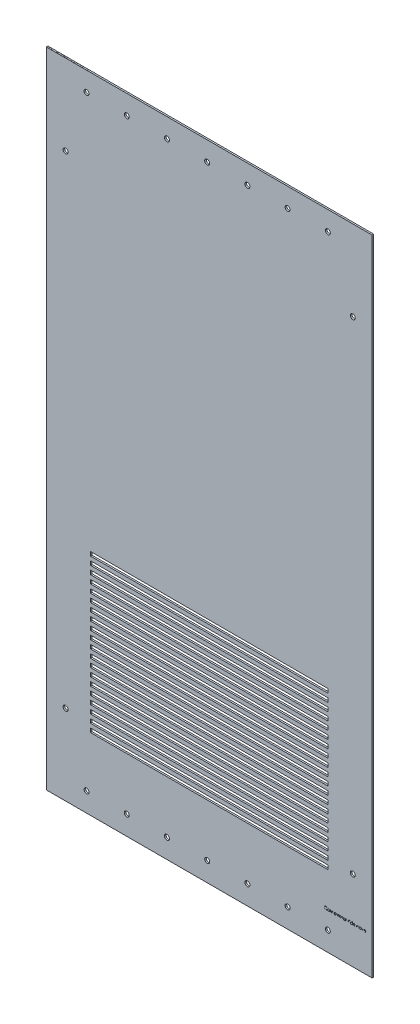
SolidWorks part; units mm, degrees
ref_plane "Front Plane" through (0, 0, 0) normal (0, 0, 1) x (1, 0, 0)
ref_plane "Top Plane" through (0, 0, 0) normal (0, 1, 0) x (1, 0, 0)
ref_plane "Right Plane" through (0, 0, 0) normal (1, 0, 0) x (0, 0, -1)
sketch "Sketch1" plane through (0, 0, 0) normal (0, 0, 1) x (1, 0, 0)
  line L0 (24, -100) -> (24, -571.3583) construction
  line L1 (0, 0) -> (405, 0)
  line L2 (0, 0) -> (0, -800)
  line L3 (0, -800) -> (405, -800)
  line L4 (405, 0) -> (405, -800)
  line L5 (24, -700) -> (381, -700) construction
  line L6 (381, -700) -> (381, -100) construction
  circle A0 centre (24, -100) radius 3.1
  circle A1 centre (381, -100) radius 3.1
  circle A2 centre (381, -700) radius 3.1
  circle A3 centre (24, -700) radius 3.1
  dimension "D8" = 6.2
  dimension "D1" = 405
  dimension "D2" = 800
  dimension "D3" = 24
  dimension "D4" = 100
  dimension "D5" = 24
  dimension "D6" = 100
  dimension "D7" = 100
extrude "Boss-Extrude1" add sketch "Sketch1" along normal blind 2
sketch "Sketch2" plane through (0, 0, 2) normal (0, 0, 1) x (1, 0, 0)
  line L0 (50, -24) -> (355, -24) construction
  line L1 (405, 0) -> (0, 0) construction
  line L2 (0, 0) -> (0, -800) construction
  line L3 (405, -800) -> (405, 0) construction
  line L4 (0, -400) -> (405, -400) construction
  line L5 (50, -776) -> (355, -776) construction
  circle A0 centre (50, -24) radius 3.1
  circle A1 centre (100, -24) radius 3.1
  circle A2 centre (150, -24) radius 3.1
  circle A3 centre (200, -24) radius 3.1
  circle A4 centre (250, -24) radius 3.1
  circle A5 centre (300, -24) radius 3.1
  circle A6 centre (350, -24) radius 3.1
  circle A7 centre (300, -776) radius 3.1
  circle A8 centre (250, -776) radius 3.1
  circle A9 centre (200, -776) radius 3.1
  circle A10 centre (150, -776) radius 3.1
  circle A11 centre (100, -776) radius 3.1
  circle A12 centre (50, -776) radius 3.1
  circle A13 centre (350, -776) radius 3.1
  dimension "D4" = 6.2
  dimension "D1" = 24
  dimension "D2" = 50
  dimension "D3" = 50
  dimension "D5" = 7
extrude "Cut-Extrude1" cut sketch "Sketch2" against normal through all
sketch "Sketch3" plane through (0, 0, 2) normal (0, 0, 1) x (1, 0, 0)
  line L0 (345.4109, -755.089) -> (399.6973, -755.089) construction
  line L1 (349.0904, -752.2312) -> (348.8156, -752.4415)
  line L2 (348.8156, -754.2364) -> (349.0904, -754.4446)
  line L3 (352.9045, -752.5313) -> (353.2186, -752.5313)
  line L4 (353.2186, -752.5313) -> (353.2186, -752.9758)
  line L5 (356.7186, -753.7035) -> (356.7186, -755.089)
  line L6 (356.7186, -755.089) -> (356.4045, -755.089)
  line L7 (356.4045, -755.089) -> (356.4045, -753.7021)
  line L8 (354.9686, -754.0941) -> (354.9686, -755.089)
  line L9 (354.9686, -755.089) -> (354.6545, -755.089)
  line L10 (354.6545, -755.089) -> (354.6545, -753.7884)
  line L11 (353.2186, -754.0127) -> (353.2186, -755.089)
  line L12 (353.2186, -755.089) -> (352.9045, -755.089)
  line L13 (352.9045, -755.089) -> (352.9045, -752.5313)
  line L14 (357.4366, -752.5313) -> (357.7507, -752.5313)
  line L15 (357.7507, -752.5313) -> (357.7507, -753.0045)
  line L16 (357.7507, -754.6255) -> (357.7507, -756.0313)
  line L17 (357.7507, -756.0313) -> (357.4366, -756.0313)
  line L18 (357.4366, -756.0313) -> (357.4366, -752.5313)
  line L19 (360.6673, -752.5313) -> (360.9814, -752.5313)
  line L20 (360.9814, -752.5313) -> (360.9814, -752.9078)
  line L21 (361.8789, -752.574) -> (361.7064, -752.8461)
  line L22 (360.9814, -754.2294) -> (360.9814, -755.089)
  line L23 (360.9814, -755.089) -> (360.6673, -755.089)
  line L24 (360.6673, -755.089) -> (360.6673, -752.5313)
  line L25 (364.2921, -754.2813) -> (364.5712, -754.4278)
  line L26 (364.7058, -753.8774) -> (362.4173, -753.8774)
  line L27 (362.4503, -753.5633) -> (364.3917, -753.5633)
  line L28 (366.5455, -752.8503) -> (366.3324, -753.0697)
  line L29 (365.1096, -754.7875) -> (365.3179, -754.5505)
  line L30 (368.4302, -752.8503) -> (368.217, -753.0697)
  line L31 (366.9943, -754.7875) -> (367.2025, -754.5505)
  line L32 (372.1994, -752.5313) -> (372.5135, -752.5313)
  line L33 (372.5135, -752.5313) -> (372.5135, -752.9078)
  line L34 (373.4109, -752.574) -> (373.2384, -752.8461)
  line L35 (372.5135, -754.2294) -> (372.5135, -755.089)
  line L36 (372.5135, -755.089) -> (372.1994, -755.089)
  line L37 (372.1994, -755.089) -> (372.1994, -752.5313)
  line L38 (376.2827, -752.8503) -> (376.0696, -753.0697)
  line L39 (374.8468, -754.7875) -> (375.0551, -754.5505)
  line L40 (376.9109, -752.5313) -> (377.225, -752.5313)
  line L41 (377.225, -752.5313) -> (377.225, -755.089)
  line L42 (377.225, -755.089) -> (376.9109, -755.089)
  line L43 (376.9109, -755.089) -> (376.9109, -752.5313)
  line L44 (380.5904, -751.4992) -> (380.5904, -755.089)
  line L45 (380.5904, -755.089) -> (380.2763, -755.089)
  line L46 (380.2763, -755.089) -> (380.2763, -754.6465)
  line L47 (380.2763, -753.0263) -> (380.2763, -751.4992)
  line L48 (380.2763, -751.4992) -> (380.5904, -751.4992)
  line L49 (383.4075, -754.2813) -> (383.6866, -754.4278)
  line L50 (383.8212, -753.8774) -> (381.5327, -753.8774)
  line L51 (381.5657, -753.5633) -> (383.5071, -753.5633)
  line L52 (388.3084, -753.0858) -> (388.0454, -753.2492)
  line L53 (388.0454, -754.371) -> (388.3084, -754.5435)
  line L54 (391.8532, -752.5313) -> (392.1933, -752.5313)
  line L55 (392.1933, -752.5313) -> (393.0423, -754.3934)
  line L56 (393.0423, -754.3934) -> (393.8914, -752.5313)
  line L57 (393.8914, -752.5313) -> (394.2314, -752.5313)
  line L58 (394.2314, -752.5313) -> (393.0648, -755.089)
  line L59 (393.0648, -755.089) -> (393.0199, -755.089)
  line L60 (393.0199, -755.089) -> (391.8532, -752.5313)
  line L61 (396.8691, -754.2813) -> (397.1481, -754.4278)
  line L62 (397.2827, -753.8774) -> (394.9943, -753.8774)
  line L63 (395.0272, -753.5633) -> (396.9686, -753.5633)
  line L64 (397.8212, -752.5313) -> (398.1353, -752.5313)
  line L65 (398.1353, -752.5313) -> (398.1353, -752.9078)
  line L66 (399.0327, -752.574) -> (398.8602, -752.8461)
  line L67 (398.1353, -754.2294) -> (398.1353, -755.089)
  line L68 (398.1353, -755.089) -> (397.8212, -755.089)
  line L69 (397.8212, -755.089) -> (397.8212, -752.5313)
  spline S0 degree 3 poles (348.8156, -752.4415) (348.7773, -752.3945) (348.7167, -752.3273) (348.629, -752.2455) (348.5611, -752.1882) (348.4894, -752.1368) (348.4155, -752.0886) (348.3383, -752.0453) (348.2316, -751.9928) (348.0919, -751.9381) (347.8544, -751.8758) (347.6689, -751.8576) (347.5437, -751.8582) knots 0 0 0 0 0.125475 0.187121 0.248294 0.309295 0.36985 0.430973 0.492456 0.616148 0.740844 1 1 1 1
  spline S1 degree 3 poles (347.5437, -751.8582) (347.4739, -751.8573) (347.3699, -751.8648) (347.2334, -751.8849) (347.1337, -751.907) (347.0362, -751.935) (346.9401, -751.9684) (346.8469, -752.0098) (346.7552, -752.0555) (346.6675, -752.1071) (346.5844, -752.1634) (346.5064, -752.2238) (346.4333, -752.2885) (346.3651, -752.3571) (346.3023, -752.4305) (346.2452, -752.5083) (346.1924, -752.5896) (346.1452, -752.6742) (346.1057, -752.7622) (346.0707, -752.8524) (346.043, -752.9455) (346.0211, -753.041) (346.0006, -753.1732) (345.9934, -753.2742) (345.9943, -753.3425) knots 0 0 0 0 0.087502 0.130463 0.172752 0.215403 0.25765 0.300153 0.343121 0.385925 0.427686 0.468818 0.509492 0.549883 0.58998 0.630405 0.670869 0.711384 0.751627 0.791776 0.832459 0.873319 0.914543 1 1 1 1
  spline S2 degree 3 poles (345.9943, -753.3425) (345.9938, -753.4441) (346.0079, -753.5941) (346.0536, -753.787) (346.1038, -753.9224) (346.1657, -754.0523) (346.2439, -754.1746) (346.3345, -754.291) (346.4388, -754.3988) (346.5532, -754.4974) (346.676, -754.5841) (346.8068, -754.6564) (346.9441, -754.7166) (347.0892, -754.7628) (347.2958, -754.8072) (347.4565, -754.8206) (347.5655, -754.8197) knots 0 0 0 0 0.12629 0.186726 0.246146 0.305576 0.365429 0.426326 0.48884 0.551725 0.613919 0.675484 0.737334 0.800229 0.864502 1 1 1 1
  spline S3 degree 3 poles (347.5655, -754.8197) (347.6856, -754.8198) (347.8641, -754.8028) (348.092, -754.7408) (348.2534, -754.677) (348.4067, -754.5939) (348.6042, -754.4576) (348.7349, -754.3292) (348.8156, -754.2364) knots 0 0 0 0 0.252949 0.374755 0.49594 0.617181 0.740909 1 1 1 1
  spline S4 degree 3 poles (349.0904, -754.4446) (349.0471, -754.5022) (348.9783, -754.5848) (348.8774, -754.6859) (348.7978, -754.756) (348.7147, -754.8222) (348.6266, -754.8825) (348.5347, -754.9378) (348.4394, -754.9884) (348.3406, -755.0333) (348.2386, -755.0718) (348.1338, -755.1049) (348.0261, -755.1321) (347.9154, -755.1534) (347.7626, -755.1727) (347.646, -755.1793) (347.5676, -755.1787) knots 0 0 0 0 0.123053 0.183475 0.243727 0.304279 0.364863 0.425946 0.487391 0.54922 0.611144 0.673529 0.736961 0.800785 0.866013 1 1 1 1
  spline S5 degree 3 poles (347.5676, -755.1787) (347.4931, -755.1796) (347.383, -755.1737) (347.2386, -755.1581) (347.1348, -755.1408) (347.0337, -755.1205) (346.9361, -755.0932) (346.8412, -755.0627) (346.7492, -755.0268) (346.6602, -754.9863) (346.5743, -754.9405) (346.4917, -754.8898) (346.4115, -754.8353) (346.3349, -754.7753) (346.236, -754.6887) (346.167, -754.6173) (346.124, -754.5666) knots 0 0 0 0 0.13775 0.203917 0.26878 0.332414 0.394754 0.45618 0.516996 0.577396 0.637198 0.696999 0.756756 0.816554 0.876948 1 1 1 1
  spline S6 degree 3 poles (346.124, -754.5666) (346.0514, -754.4819) (345.954, -754.3461) (345.8508, -754.1497) (345.7884, -753.9964) (345.7397, -753.8363) (345.6937, -753.6109) (345.6798, -753.4365) (345.6802, -753.3186) knots 0 0 0 0 0.247156 0.36878 0.490734 0.613614 0.738958 1 1 1 1
  spline S7 degree 3 poles (345.6802, -753.3186) (345.6801, -753.1948) (345.6958, -753.0113) (345.7526, -752.7759) (345.812, -752.6097) (345.8873, -752.4505) (345.9803, -752.2997) (346.09, -752.1562) (346.2154, -752.0222) (346.353, -751.8996) (346.5003, -751.7918) (346.6571, -751.7021) (346.8216, -751.6271) (346.9951, -751.5695) (347.2417, -751.5146) (347.4336, -751.4995) (347.5634, -751.4992) knots 0 0 0 0 0.127014 0.187955 0.248014 0.307748 0.368235 0.42947 0.492743 0.556258 0.618217 0.679655 0.741246 0.803415 0.866815 1 1 1 1
  spline S8 degree 3 poles (347.5634, -751.4992) (347.6429, -751.4991) (347.7611, -751.5045) (347.9156, -751.5255) (348.0272, -751.5466) (348.1363, -751.5728) (348.2421, -751.6069) (348.3452, -751.646) (348.445, -751.6909) (348.5409, -751.7414) (348.6329, -751.7968) (348.7204, -751.8571) (348.8039, -751.9218) (348.882, -751.9922) (348.9822, -752.0913) (349.0482, -752.1745) (349.0904, -752.2312) knots 0 0 0 0 0.135683 0.201215 0.265682 0.329267 0.392395 0.45507 0.517127 0.57879 0.63974 0.700192 0.759806 0.819628 0.879355 1 1 1 1
  spline S9 degree 3 poles (350.954, -752.4864) (351.0481, -752.4854) (351.1873, -752.499) (351.3654, -752.5436) (351.4912, -752.5888) (351.6096, -752.6496) (351.762, -752.7471) (351.8636, -752.8398) (351.9257, -752.9078) knots 0 0 0 0 0.258332 0.382134 0.503804 0.624693 0.746871 1 1 1 1
  spline S10 degree 3 poles (351.9257, -752.9078) (351.9828, -752.9701) (352.0592, -753.07) (352.1414, -753.2144) (352.1905, -753.3266) (352.2292, -753.443) (352.2663, -753.6059) (352.2758, -753.7322) (352.2763, -753.8171) knots 0 0 0 0 0.253834 0.376506 0.498534 0.621368 0.744565 1 1 1 1
  spline S11 degree 3 poles (352.2763, -753.8171) (352.2768, -753.9027) (352.2651, -754.0298) (352.2265, -754.1942) (352.1857, -754.3121) (352.1333, -754.4259) (352.0694, -754.5353) (351.9936, -754.6405) (351.9076, -754.7405) (351.8125, -754.8327) (351.7094, -754.913) (351.6002, -754.9818) (351.4836, -755.0373) (351.3605, -755.0809) (351.1845, -755.1228) (351.0469, -755.1335) (350.954, -755.1338) knots 0 0 0 0 0.123337 0.183265 0.243172 0.302898 0.363774 0.425605 0.489659 0.553785 0.616222 0.677854 0.739517 0.802097 0.865866 1 1 1 1
  spline S12 degree 3 poles (350.954, -755.1338) (350.8606, -755.1334) (350.7226, -755.1229) (350.546, -755.0809) (350.4228, -755.0371) (350.3057, -754.9818) (350.1959, -754.9132) (350.0927, -754.8326) (349.9976, -754.7405) (349.9116, -754.6405) (349.8357, -754.5353) (349.7719, -754.4259) (349.7195, -754.3121) (349.6787, -754.1942) (349.6401, -754.0298) (349.6284, -753.9027) (349.6289, -753.8171) knots 0 0 0 0 0.134635 0.198324 0.260825 0.322714 0.384555 0.446913 0.510958 0.574931 0.636685 0.697483 0.757134 0.816966 0.876818 1 1 1 1
  spline S13 degree 3 poles (349.6289, -753.8171) (349.6294, -753.7324) (349.6389, -753.6064) (349.6759, -753.4439) (349.7146, -753.328) (349.7642, -753.2162) (349.8453, -753.0715) (349.923, -752.9724) (349.9794, -752.9099) knots 0 0 0 0 0.255238 0.378679 0.501088 0.622714 0.746241 1 1 1 1
  spline S14 degree 3 poles (349.9794, -752.9099) (350.041, -752.841) (350.1436, -752.7492) (350.2956, -752.6497) (350.4153, -752.5901) (350.5409, -752.5434) (350.7198, -752.499) (350.8594, -752.4855) (350.954, -752.4864) knots 0 0 0 0 0.252713 0.374819 0.496436 0.617911 0.741288 1 1 1 1
  spline S15 degree 3 poles (350.9526, -752.8005) (350.8856, -752.8007) (350.7861, -752.8097) (350.6581, -752.8408) (350.5667, -752.8734) (350.479, -752.9155) (350.3951, -752.9672) (350.3147, -753.0278) (350.2393, -753.0973) (350.1701, -753.1732) (350.1096, -753.254) (350.0582, -753.3385) (350.0154, -753.4268) (349.9835, -753.5197) (349.952, -753.6499) (349.9432, -753.7511) (349.943, -753.8192) knots 0 0 0 0 0.126044 0.187165 0.247399 0.30838 0.36978 0.432584 0.497641 0.562401 0.625557 0.687332 0.748313 0.809791 0.871768 1 1 1 1
  spline S16 degree 3 poles (349.943, -753.8192) (349.9432, -753.9079) (349.9588, -754.0412) (350.0171, -754.2092) (350.0757, -754.3288) (350.1491, -754.4395) (350.2356, -754.5382) (350.3342, -754.6233) (350.4438, -754.694) (350.5622, -754.7501) (350.7306, -754.804) (350.8633, -754.8207) (350.9526, -754.8197) knots 0 0 0 0 0.168179 0.251488 0.335841 0.419834 0.502345 0.583649 0.665931 0.748717 0.831047 1 1 1 1
  spline S17 degree 3 poles (350.9526, -754.8197) (351.0419, -754.8206) (351.1744, -754.8042) (351.3425, -754.7499) (351.4607, -754.6941) (351.5703, -754.6231) (351.6696, -754.5386) (351.7554, -754.4392) (351.8287, -754.3287) (351.8882, -754.2094) (351.9462, -754.0412) (351.962, -753.9079) (351.9622, -753.8192) knots 0 0 0 0 0.168983 0.250908 0.333708 0.416005 0.49766 0.579893 0.663902 0.748466 0.831791 1 1 1 1
  spline S18 degree 3 poles (351.9622, -753.8192) (351.962, -753.7511) (351.9531, -753.6499) (351.9217, -753.5197) (351.8898, -753.4268) (351.8471, -753.3383) (351.7947, -753.2543) (351.7345, -753.1729) (351.6644, -753.0975) (351.5891, -753.0278) (351.5087, -752.9672) (351.4249, -752.9157) (351.3375, -752.873) (351.2461, -752.8411) (351.1185, -752.8095) (351.0193, -752.8008) (350.9526, -752.8005) knots 0 0 0 0 0.128274 0.19027 0.251768 0.312769 0.374793 0.43797 0.503047 0.568125 0.63095 0.692369 0.752973 0.813641 0.874355 1 1 1 1
  spline S19 degree 3 poles (353.2186, -752.9758) (353.2713, -752.9003) (353.3777, -752.7674) (353.5077, -752.6573) (353.5734, -752.6161) knots 0 0 0 0 0.543395 1 1 1 1
  spline S20 degree 3 poles (353.5734, -752.6161) (353.655, -752.574) (353.8268, -752.5073) (354.0099, -752.4871) (354.1006, -752.4864) knots 0 0 0 0 0.503035 1 1 1 1
  spline S21 degree 3 poles (354.1006, -752.4864) (354.1617, -752.4872) (354.2533, -752.4949) (354.3711, -752.5263) (354.4557, -752.5586) (354.5354, -752.5979) (354.6085, -752.6439) (354.6741, -752.6956) (354.7323, -752.7553) (354.7845, -752.8246) (354.8523, -752.9384) (354.8911, -753.0355) (354.9146, -753.1041) knots 0 0 0 0 0.166532 0.248836 0.331246 0.412957 0.490494 0.566156 0.639987 0.716765 0.802144 1 1 1 1
  spline S22 degree 3 poles (354.9146, -753.1041) (354.9407, -753.055) (354.9838, -752.9846) (355.0481, -752.8974) (355.0981, -752.8374) (355.1506, -752.7821) (355.2056, -752.7313) (355.263, -752.6848) (355.3428, -752.6305) (355.4466, -752.5729) (355.6212, -752.5057) (355.7604, -752.4862) (355.8527, -752.4864) knots 0 0 0 0 0.141226 0.209116 0.27484 0.339483 0.402476 0.464942 0.526833 0.647415 0.765562 1 1 1 1
  spline S23 degree 3 poles (355.8527, -752.4864) (355.9364, -752.487) (356.0614, -752.5007) (356.2157, -752.5587) (356.3211, -752.6169) (356.4163, -752.6901) (356.499, -752.7772) (356.5688, -752.8775) (356.6144, -752.9719) (356.6453, -753.0553) (356.6643, -753.1263) (356.6812, -753.2044) (356.6952, -753.2898) (356.7054, -753.3827) (356.7159, -753.5213) (356.719, -753.6292) (356.7186, -753.7035) knots 0 0 0 0 0.147965 0.218797 0.28947 0.359724 0.429708 0.500497 0.574429 0.613947 0.657155 0.703973 0.754939 0.809707 0.868833 1 1 1 1
  spline S24 degree 3 poles (356.4045, -753.7021) (356.4046, -753.6393) (356.4036, -753.5489) (356.3965, -753.434) (356.3906, -753.3598) (356.3823, -753.2936) (356.3717, -753.2354) (356.3604, -753.1848) (356.3417, -753.1287) (356.3117, -753.0668) (356.2661, -753.0001) (356.2086, -752.942) (356.1423, -752.8916) (356.0667, -752.8507) (355.9529, -752.8104) (355.8605, -752.8001) (355.798, -752.8005) knots 0 0 0 0 0.150563 0.216151 0.27568 0.328707 0.375904 0.417302 0.452693 0.517265 0.581217 0.645322 0.712024 0.78013 0.850218 1 1 1 1
  spline S25 degree 3 poles (355.798, -752.8005) (355.7195, -752.7991) (355.6025, -752.8184) (355.4556, -752.8764) (355.3533, -752.9388) (355.2593, -753.0136) (355.1784, -753.1026) (355.1116, -753.2032) (355.0663, -753.2963) (355.0377, -753.38) (355.0189, -753.4531) (355.0042, -753.5362) (354.9904, -753.6287) (354.9814, -753.7313) (354.9701, -753.8872) (354.9691, -754.0095) (354.9686, -754.0941) knots 0 0 0 0 0.134707 0.201865 0.270788 0.340024 0.408083 0.476813 0.547346 0.58564 0.628865 0.677153 0.730803 0.789807 0.854325 1 1 1 1
  spline S26 degree 3 poles (354.6545, -753.7884) (354.6546, -753.7178) (354.6536, -753.6165) (354.6465, -753.4878) (354.6406, -753.405) (354.6322, -753.3315) (354.6226, -753.2671) (354.6112, -753.2119) (354.5924, -753.1514) (354.5637, -753.0846) (354.5175, -753.0135) (354.4599, -752.9512) (354.3923, -752.8981) (354.3163, -752.8542) (354.202, -752.8109) (354.1086, -752.801) (354.0459, -752.8005) knots 0 0 0 0 0.158779 0.227738 0.289946 0.345499 0.393896 0.436374 0.472122 0.536384 0.599078 0.661948 0.726311 0.791771 0.858647 1 1 1 1
  spline S27 degree 3 poles (354.0459, -752.8005) (353.9701, -752.7999) (353.8562, -752.8181) (353.7134, -752.8756) (353.6114, -752.9352) (353.5177, -753.0091) (353.4357, -753.096) (353.3668, -753.1949) (353.3211, -753.287) (353.2916, -753.3686) (353.272, -753.4379) (353.2551, -753.5149) (353.2426, -753.5998) (353.2305, -753.6921) (353.2224, -753.8306) (353.2176, -753.9383) (353.2186, -754.0127) knots 0 0 0 0 0.136871 0.206114 0.277538 0.349772 0.421251 0.492911 0.567027 0.606614 0.649704 0.697303 0.749086 0.804881 0.865485 1 1 1 1
  spline S28 degree 3 poles (357.7507, -753.0045) (357.8128, -752.9192) (357.9173, -752.8033) (358.0785, -752.6791) (358.2057, -752.6077) (358.3401, -752.5539) (358.5313, -752.4998) (358.6824, -752.4867) (358.7841, -752.4864) knots 0 0 0 0 0.263045 0.386061 0.505771 0.625178 0.746148 1 1 1 1
  spline S29 degree 3 poles (358.7841, -752.4864) (358.8738, -752.4873) (359.007, -752.4972) (359.1785, -752.538) (359.3, -752.5814) (359.4173, -752.635) (359.5285, -752.7028) (359.6354, -752.7812) (359.7354, -752.8714) (359.8277, -752.969) (359.9075, -753.0741) (359.9764, -753.183) (360.0321, -753.2976) (360.0756, -753.4169) (360.1176, -753.5847) (360.1284, -753.7153) (360.1289, -753.8031) knots 0 0 0 0 0.128636 0.190653 0.252125 0.313446 0.375227 0.438498 0.503285 0.56801 0.630879 0.692154 0.752552 0.813191 0.873985 1 1 1 1
  spline S30 degree 3 poles (360.1289, -753.8031) (360.1287, -753.8926) (360.1171, -754.0253) (360.0765, -754.196) (360.0335, -754.3173) (359.9778, -754.4333) (359.9101, -754.5439) (359.8302, -754.6491) (359.7389, -754.7474) (359.6399, -754.838) (359.534, -754.9173) (359.4229, -754.9838) (359.3073, -755.0394) (359.186, -755.0812) (359.0157, -755.1222) (358.8832, -755.1335) (358.7939, -755.1338) knots 0 0 0 0 0.128034 0.189574 0.25058 0.311733 0.37325 0.435763 0.500346 0.564949 0.627528 0.689157 0.749865 0.81076 0.8723 1 1 1 1
  spline S31 degree 3 poles (358.7939, -755.1338) (358.6935, -755.135) (358.545, -755.1178) (358.3546, -755.0653) (358.2204, -755.0086) (358.0923, -754.9363) (357.9272, -754.8168) (357.8182, -754.7057) (357.7507, -754.6255) knots 0 0 0 0 0.250548 0.37123 0.492116 0.613401 0.737997 1 1 1 1
  spline S32 degree 3 poles (358.7813, -752.8005) (358.7112, -752.7995) (358.6078, -752.8095) (358.4741, -752.8391) (358.38, -752.872) (358.2897, -752.9124) (358.2041, -752.9629) (358.123, -753.0226) (358.0468, -753.0902) (357.9779, -753.1648) (357.917, -753.2444) (357.8657, -753.3289) (357.8232, -753.4175) (357.7909, -753.511) (357.7597, -753.6431) (357.7509, -753.7462) (357.7507, -753.8157) knots 0 0 0 0 0.130024 0.192374 0.253884 0.314896 0.375806 0.438242 0.501591 0.564881 0.626533 0.687516 0.748106 0.808796 0.870822 1 1 1 1
  spline S33 degree 3 poles (357.7507, -753.8157) (357.7508, -753.9065) (357.766, -754.0416) (357.822, -754.2114) (357.8805, -754.3289) (357.9544, -754.4369) (358.0435, -754.5336) (358.147, -754.6183) (358.263, -754.6898) (358.3875, -754.7477) (358.5606, -754.8034) (358.6961, -754.8196) (358.7862, -754.8197) knots 0 0 0 0 0.169344 0.251061 0.332326 0.413189 0.494299 0.576654 0.661785 0.747765 0.831967 1 1 1 1
  spline S34 degree 3 poles (358.7862, -754.8197) (358.8747, -754.8203) (359.0069, -754.8024) (359.1758, -754.7474) (359.296, -754.688) (359.4088, -754.6149) (359.5107, -754.5274) (359.5997, -754.4259) (359.6756, -754.3129) (359.7366, -754.1917) (359.7979, -754.0253) (359.8138, -753.8934) (359.8148, -753.8066) knots 0 0 0 0 0.165574 0.248159 0.332033 0.416257 0.499525 0.583039 0.668596 0.754035 0.83692 1 1 1 1
  spline S35 degree 3 poles (359.8148, -753.8066) (359.816, -753.7191) (359.7964, -753.5882) (359.7389, -753.4207) (359.6764, -753.3012) (359.6022, -753.1884) (359.5125, -753.0889) (359.4118, -753.0017) (359.2992, -752.9297) (359.1782, -752.8725) (359.0072, -752.8159) (358.8718, -752.8009) (358.7813, -752.8005) knots 0 0 0 0 0.163349 0.245826 0.330367 0.415198 0.497941 0.580476 0.66374 0.747513 0.830399 1 1 1 1
  spline S36 degree 3 poles (360.9814, -752.9078) (361.0245, -752.8401) (361.0924, -752.7463) (361.1982, -752.6436) (361.2758, -752.5851) (361.3562, -752.5413) (361.4638, -752.4986) (361.5494, -752.4868) (361.6054, -752.4864) knots 0 0 0 0 0.306112 0.438367 0.560541 0.675317 0.786114 1 1 1 1
  spline S37 degree 3 poles (361.6054, -752.4864) (361.6504, -752.4867) (361.7469, -752.5036) (361.8345, -752.5472) (361.8789, -752.574) knots 0 0 0 0 0.463523 1 1 1 1
  spline S38 degree 3 poles (361.7064, -752.8461) (361.6778, -752.8334) (361.6263, -752.8101) (361.5705, -752.8008) (361.5458, -752.8005) knots 0 0 0 0 0.56023 1 1 1 1
  spline S39 degree 3 poles (361.5458, -752.8005) (361.4943, -752.8004) (361.4154, -752.8193) (361.3205, -752.8761) (361.2623, -752.9243) (361.2173, -752.9709) (361.1851, -753.0115) (361.1557, -753.0571) (361.1275, -753.1068) (361.1018, -753.1616) (361.069, -753.2426) (361.0494, -753.3071) (361.0375, -753.3516) knots 0 0 0 0 0.191338 0.295191 0.410312 0.47193 0.536425 0.603119 0.674118 0.749332 0.828283 1 1 1 1
  spline S40 degree 3 poles (361.0375, -753.3516) (361.0258, -753.3962) (361.0143, -753.4714) (361.0021, -753.5811) (360.9949, -753.6841) (360.9884, -753.8007) (360.9831, -753.984) (360.9809, -754.1284) (360.9814, -754.2294) knots 0 0 0 0 0.156938 0.2586 0.375891 0.508166 0.656238 1 1 1 1
  spline S41 degree 3 poles (364.5712, -754.4278) (364.5297, -754.5055) (364.4602, -754.6145) (364.3533, -754.7442) (364.2682, -754.826) (364.1785, -754.8972) (364.0838, -754.9596) (363.9835, -755.0127) (363.8776, -755.0575) (363.7653, -755.0918) (363.603, -755.1252) (363.4761, -755.1338) (363.3898, -755.1338) knots 0 0 0 0 0.181661 0.265874 0.346355 0.4246 0.501903 0.579992 0.658443 0.738672 0.821894 1 1 1 1
  spline S42 degree 3 poles (363.3898, -755.1338) (363.294, -755.1338) (363.1531, -755.1228) (362.9739, -755.0796) (362.8507, -755.0357) (362.7359, -754.9783) (362.6294, -754.9083) (362.5306, -754.8262) (362.4426, -754.7312) (362.3633, -754.6295) (362.2934, -754.5235) (362.2349, -754.4136) (362.1874, -754.3003) (362.149, -754.1844) (362.1129, -754.024) (362.1041, -753.9001) (362.1032, -753.8171) knots 0 0 0 0 0.139629 0.204797 0.268135 0.329814 0.391301 0.453434 0.516552 0.579631 0.641119 0.701294 0.76081 0.819932 0.87892 1 1 1 1
  spline S43 degree 3 poles (362.1032, -753.8171) (362.1042, -753.7393) (362.1115, -753.6232) (362.1431, -753.4727) (362.1752, -753.3638) (362.2168, -753.2582) (362.285, -753.1207) (362.3501, -753.0246) (362.3977, -752.9632) knots 0 0 0 0 0.253768 0.377428 0.500551 0.623296 0.746578 1 1 1 1
  spline S44 degree 3 poles (362.3977, -752.9632) (362.4583, -752.8874) (362.557, -752.7815) (362.7117, -752.6708) (362.8333, -752.6027) (362.9636, -752.5511) (363.1502, -752.4986) (363.298, -752.4876) (363.3975, -752.4864) knots 0 0 0 0 0.253589 0.374643 0.49534 0.616325 0.739759 1 1 1 1
  spline S45 degree 3 poles (363.3975, -752.4864) (363.5003, -752.486) (363.6522, -752.5008) (363.8448, -752.5541) (363.9787, -752.6092) (364.1043, -752.6804) (364.2626, -752.7995) (364.3661, -752.9091) (364.4274, -752.9898) knots 0 0 0 0 0.259033 0.38188 0.502258 0.622752 0.744743 1 1 1 1
  spline S46 degree 3 poles (364.4274, -752.9898) (364.4733, -753.0487) (364.5332, -753.1443) (364.5969, -753.2811) (364.6352, -753.39) (364.6662, -753.5038) (364.6968, -753.6662) (364.7042, -753.7922) (364.7058, -753.8774) knots 0 0 0 0 0.236255 0.356174 0.47725 0.60154 0.729618 1 1 1 1
  spline S47 degree 3 poles (362.4173, -753.8774) (362.4191, -753.9437) (362.428, -754.0415) (362.4583, -754.1667) (362.4895, -754.2538) (362.5274, -754.3367) (362.5738, -754.4149) (362.6291, -754.4879) (362.6908, -754.5565) (362.7596, -754.6176) (362.8318, -754.6722) (362.9087, -754.718) (362.9896, -754.7552) (363.0744, -754.7843) (363.1944, -754.8114) (363.2875, -754.8201) (363.3505, -754.8197) knots 0 0 0 0 0.134476 0.198391 0.260753 0.321829 0.383037 0.444653 0.507398 0.569825 0.630778 0.690929 0.750945 0.811049 0.872331 1 1 1 1
  spline S48 degree 3 poles (363.3505, -754.8197) (363.4127, -754.82) (363.506, -754.8127) (363.6279, -754.7872) (363.7171, -754.7613) (363.8027, -754.7297) (363.8819, -754.6916) (363.9548, -754.6495) (364.0229, -754.6013) (364.089, -754.5423) (364.1825, -754.4374) (364.2496, -754.3478) (364.2921, -754.2813) knots 0 0 0 0 0.163879 0.245659 0.327726 0.40861 0.485749 0.559169 0.630268 0.705306 0.792065 1 1 1 1
  spline S49 degree 3 poles (364.3917, -753.5633) (364.3718, -753.4826) (364.3322, -753.3687) (364.2597, -753.2317) (364.1981, -753.1462) (364.1283, -753.0702) (364.0477, -753.0037) (363.9572, -752.9443) (363.8575, -752.8941) (363.7518, -752.8515) (363.604, -752.813) (363.4901, -752.7994) (363.4136, -752.8005) knots 0 0 0 0 0.185231 0.267501 0.3444 0.419595 0.496891 0.576638 0.660268 0.745387 0.83004 1 1 1 1
  spline S50 degree 3 poles (363.4136, -752.8005) (363.3517, -752.8003) (363.2597, -752.807) (363.1413, -752.8328) (363.0566, -752.8587) (362.976, -752.8933) (362.871, -752.9477) (362.8001, -753.002) (362.7546, -753.0403) knots 0 0 0 0 0.259141 0.384162 0.505992 0.629098 0.750669 1 1 1 1
  spline S51 degree 3 poles (362.7546, -753.0403) (362.7197, -753.0697) (362.6725, -753.1205) (362.6158, -753.1953) (362.5764, -753.2583) (362.5403, -753.327) (362.4941, -753.4276) (362.4667, -753.508) (362.4503, -753.5633) knots 0 0 0 0 0.22258 0.3385 0.458709 0.585535 0.717518 1 1 1 1
  spline S52 degree 3 poles (366.3324, -753.0697) (366.2976, -753.0282) (366.2441, -752.9703) (366.1663, -752.9063) (366.1112, -752.8673) (366.0558, -752.8379) (365.9837, -752.8096) (365.9275, -752.8005) (365.8907, -752.8005) knots 0 0 0 0 0.305036 0.441309 0.565963 0.683525 0.793334 1 1 1 1
  spline S53 degree 3 poles (365.8907, -752.8005) (365.847, -752.7996) (365.7819, -752.8137) (365.7046, -752.8573) (365.6544, -752.9032) (365.612, -752.9559) (365.5703, -753.0348) (365.5585, -753.1008) (365.5584, -753.1447) knots 0 0 0 0 0.245901 0.369166 0.498511 0.628504 0.751028 1 1 1 1
  spline S54 degree 3 poles (365.5584, -753.1447) (365.5584, -753.1851) (365.5741, -753.2693) (365.6186, -753.3423) (365.6453, -753.3768) knots 0 0 0 0 0.479403 1 1 1 1
  spline S55 degree 3 poles (365.6453, -753.3768) (365.6613, -753.3985) (365.6925, -753.4281) (365.7381, -753.4682) (365.7814, -753.5002) (365.8301, -753.5338) (365.907, -753.5812) (365.9672, -753.6178) (366.0106, -753.6404) knots 0 0 0 0 0.17756 0.283982 0.402217 0.533568 0.676121 1 1 1 1
  spline S56 degree 3 poles (366.0106, -753.6404) (366.0633, -753.6696) (366.1392, -753.7134) (366.2328, -753.7763) (366.2943, -753.8209) (366.3482, -753.8661) (366.4099, -753.9223) (366.4491, -753.9681) (366.4712, -753.9994) knots 0 0 0 0 0.307115 0.446213 0.574876 0.694152 0.804581 1 1 1 1
  spline S57 degree 3 poles (366.4712, -753.9994) (366.5093, -754.0569) (366.5733, -754.1836) (366.5894, -754.3246) (366.5904, -754.3948) knots 0 0 0 0 0.495235 1 1 1 1
  spline S58 degree 3 poles (366.5904, -754.3948) (366.5899, -754.4446) (366.5844, -754.5186) (366.5614, -754.6134) (366.5384, -754.6811) (366.5072, -754.745) (366.4706, -754.8069) (366.4268, -754.8652) (366.3767, -754.9201) (366.3218, -754.9702) (366.2633, -755.0142) (366.2011, -755.0508) (366.1355, -755.081) (366.0666, -755.1051) (365.9686, -755.1277) (365.8923, -755.1335) (365.8409, -755.1338) knots 0 0 0 0 0.127199 0.188597 0.24864 0.309525 0.370037 0.431889 0.495704 0.559519 0.621372 0.682397 0.743568 0.805498 0.86864 1 1 1 1
  spline S59 degree 3 poles (365.8409, -755.1338) (365.7706, -755.1344) (365.6655, -755.1222) (365.5299, -755.0835) (365.4315, -755.0439) (365.3385, -754.9937) (365.2253, -754.9141) (365.1519, -754.8411) (365.1096, -754.7875) knots 0 0 0 0 0.251724 0.377219 0.504694 0.631458 0.755401 1 1 1 1
  spline S60 degree 3 poles (365.3179, -754.5505) (365.3555, -754.5924) (365.4138, -754.6511) (365.4997, -754.7146) (365.5625, -754.7532) (365.6267, -754.783) (365.7132, -754.8109) (365.7803, -754.8199) (365.8248, -754.8197) knots 0 0 0 0 0.285904 0.417172 0.540501 0.659238 0.775006 1 1 1 1
  spline S61 degree 3 poles (365.8248, -754.8197) (365.884, -754.8202) (365.9718, -754.8049) (366.0775, -754.7532) (366.1456, -754.6992) (366.2034, -754.6362) (366.2595, -754.5419) (366.2766, -754.4614) (366.2763, -754.4082) knots 0 0 0 0 0.261896 0.387836 0.517686 0.644509 0.764718 1 1 1 1
  spline S62 degree 3 poles (366.2763, -754.4082) (366.2761, -754.3642) (366.2621, -754.2759) (366.218, -754.1981) (366.1901, -754.1642) knots 0 0 0 0 0.500453 1 1 1 1
  spline S63 degree 3 poles (366.1901, -754.1642) (366.1732, -754.1439) (366.142, -754.1145) (366.0941, -754.0764) (366.049, -754.0441) (365.997, -754.0105) (365.9143, -753.9619) (365.8487, -753.925) (365.8023, -753.9006) knots 0 0 0 0 0.167462 0.27227 0.389551 0.520801 0.666263 1 1 1 1
  spline S64 degree 3 poles (365.8023, -753.9006) (365.7518, -753.8726) (365.6788, -753.8309) (365.5897, -753.7692) (365.5306, -753.7263) (365.4785, -753.6829) (365.4205, -753.6265) (365.3823, -753.5825) (365.3613, -753.5514) knots 0 0 0 0 0.30595 0.443775 0.572824 0.692154 0.802296 1 1 1 1
  spline S65 degree 3 poles (365.3613, -753.5514) (365.3221, -753.495) (365.2637, -753.3671) (365.243, -753.2281) (365.2443, -753.1574) knots 0 0 0 0 0.492591 1 1 1 1
  spline S66 degree 3 poles (365.2443, -753.1574) (365.2446, -753.1112) (365.2487, -753.0426) (365.2694, -752.955) (365.2884, -752.8929) (365.3149, -752.8344) (365.3466, -752.7787) (365.3837, -752.726) (365.4266, -752.677) (365.4737, -752.6325) (365.5246, -752.5937) (365.5781, -752.5606) (365.6345, -752.5328) (365.6944, -752.5118) (365.7795, -752.4921) (365.8458, -752.4859) (365.8907, -752.4864) knots 0 0 0 0 0.133044 0.196507 0.258613 0.319728 0.380873 0.442636 0.505079 0.567881 0.628814 0.68891 0.748765 0.809386 0.870884 1 1 1 1
  spline S67 degree 3 poles (365.8907, -752.4864) (365.9456, -752.4864) (366.0295, -752.4981) (366.1374, -752.5366) (366.2197, -752.5768) (366.3015, -752.6289) (366.415, -752.7158) (366.4949, -752.793) (366.5455, -752.8503) knots 0 0 0 0 0.213412 0.326127 0.444452 0.569061 0.702712 1 1 1 1
  spline S68 degree 3 poles (368.217, -753.0697) (368.1822, -753.0282) (368.1287, -752.9703) (368.0509, -752.9063) (367.9959, -752.8673) (367.9404, -752.8379) (367.8683, -752.8096) (367.8121, -752.8005) (367.7753, -752.8005) knots 0 0 0 0 0.305036 0.441309 0.565963 0.683525 0.793334 1 1 1 1
  spline S69 degree 3 poles (367.7753, -752.8005) (367.7317, -752.7996) (367.6665, -752.8137) (367.5892, -752.8573) (367.5391, -752.9032) (367.4966, -752.9559) (367.4549, -753.0348) (367.4431, -753.1008) (367.443, -753.1447) knots 0 0 0 0 0.245901 0.369166 0.498511 0.628504 0.751028 1 1 1 1
  spline S70 degree 3 poles (367.443, -753.1447) (367.443, -753.1851) (367.4587, -753.2693) (367.5032, -753.3423) (367.5299, -753.3768) knots 0 0 0 0 0.479403 1 1 1 1
  spline S71 degree 3 poles (367.5299, -753.3768) (367.5459, -753.3985) (367.5771, -753.4281) (367.6227, -753.4682) (367.666, -753.5002) (367.7147, -753.5338) (367.7916, -753.5812) (367.8518, -753.6178) (367.8952, -753.6404) knots 0 0 0 0 0.17756 0.283982 0.402217 0.533568 0.676121 1 1 1 1
  spline S72 degree 3 poles (367.8952, -753.6404) (367.9479, -753.6696) (368.0238, -753.7134) (368.1175, -753.7763) (368.1789, -753.8209) (368.2328, -753.8661) (368.2945, -753.9223) (368.3337, -753.9681) (368.3558, -753.9994) knots 0 0 0 0 0.307115 0.446213 0.574876 0.694152 0.804581 1 1 1 1
  spline S73 degree 3 poles (368.3558, -753.9994) (368.3939, -754.0569) (368.458, -754.1836) (368.474, -754.3246) (368.475, -754.3948) knots 0 0 0 0 0.495235 1 1 1 1
  spline S74 degree 3 poles (368.475, -754.3948) (368.4746, -754.4446) (368.4691, -754.5186) (368.4461, -754.6134) (368.423, -754.6811) (368.3918, -754.745) (368.3552, -754.8069) (368.3114, -754.8652) (368.2613, -754.9201) (368.2064, -754.9702) (368.1479, -755.0142) (368.0857, -755.0508) (368.0202, -755.081) (367.9512, -755.1051) (367.8532, -755.1277) (367.7769, -755.1335) (367.7255, -755.1338) knots 0 0 0 0 0.127199 0.188597 0.24864 0.309525 0.370037 0.431889 0.495704 0.559519 0.621372 0.682397 0.743568 0.805498 0.86864 1 1 1 1
  spline S75 degree 3 poles (367.7255, -755.1338) (367.6553, -755.1344) (367.5501, -755.1222) (367.4145, -755.0835) (367.3161, -755.0439) (367.2231, -754.9937) (367.1099, -754.9141) (367.0365, -754.8411) (366.9943, -754.7875) knots 0 0 0 0 0.251724 0.377219 0.504694 0.631458 0.755401 1 1 1 1
  spline S76 degree 3 poles (367.2025, -754.5505) (367.2401, -754.5924) (367.2984, -754.6511) (367.3843, -754.7146) (367.4471, -754.7532) (367.5113, -754.783) (367.5978, -754.8109) (367.6649, -754.8199) (367.7094, -754.8197) knots 0 0 0 0 0.285904 0.417172 0.540501 0.659238 0.775006 1 1 1 1
  spline S77 degree 3 poles (367.7094, -754.8197) (367.7686, -754.8202) (367.8564, -754.8049) (367.9621, -754.7532) (368.0302, -754.6992) (368.088, -754.6362) (368.1441, -754.5419) (368.1613, -754.4614) (368.1609, -754.4082) knots 0 0 0 0 0.261896 0.387836 0.517686 0.644509 0.764718 1 1 1 1
  spline S78 degree 3 poles (368.1609, -754.4082) (368.1608, -754.3642) (368.1468, -754.2759) (368.1026, -754.1981) (368.0747, -754.1642) knots 0 0 0 0 0.500453 1 1 1 1
  spline S79 degree 3 poles (368.0747, -754.1642) (368.0578, -754.1439) (368.0266, -754.1145) (367.9787, -754.0764) (367.9336, -754.0441) (367.8816, -754.0105) (367.799, -753.9619) (367.7333, -753.925) (367.687, -753.9006) knots 0 0 0 0 0.167462 0.27227 0.389551 0.520801 0.666263 1 1 1 1
  spline S80 degree 3 poles (367.687, -753.9006) (367.6364, -753.8726) (367.5634, -753.8309) (367.4743, -753.7692) (367.4152, -753.7263) (367.3631, -753.6829) (367.3052, -753.6265) (367.2669, -753.5825) (367.246, -753.5514) knots 0 0 0 0 0.30595 0.443775 0.572824 0.692154 0.802296 1 1 1 1
  spline S81 degree 3 poles (367.246, -753.5514) (367.2067, -753.495) (367.1483, -753.3671) (367.1276, -753.2281) (367.1289, -753.1574) knots 0 0 0 0 0.492591 1 1 1 1
  spline S82 degree 3 poles (367.1289, -753.1574) (367.1292, -753.1112) (367.1333, -753.0426) (367.154, -752.955) (367.173, -752.8929) (367.1995, -752.8344) (367.2312, -752.7787) (367.2684, -752.726) (367.3112, -752.677) (367.3583, -752.6325) (367.4092, -752.5937) (367.4627, -752.5606) (367.5191, -752.5328) (367.579, -752.5118) (367.6641, -752.4921) (367.7304, -752.4859) (367.7753, -752.4864) knots 0 0 0 0 0.133044 0.196507 0.258613 0.319728 0.380873 0.442636 0.505079 0.567881 0.628814 0.68891 0.748765 0.809386 0.870884 1 1 1 1
  spline S83 degree 3 poles (367.7753, -752.4864) (367.8302, -752.4864) (367.9141, -752.4981) (368.022, -752.5366) (368.1043, -752.5768) (368.1861, -752.6289) (368.2996, -752.7158) (368.3795, -752.793) (368.4302, -752.8503) knots 0 0 0 0 0.213412 0.326127 0.444452 0.569061 0.702712 1 1 1 1
  spline S84 degree 3 poles (370.3386, -752.4864) (370.4327, -752.4854) (370.5719, -752.499) (370.75, -752.5436) (370.8758, -752.5888) (370.9942, -752.6496) (371.1466, -752.7471) (371.2482, -752.8398) (371.3104, -752.9078) knots 0 0 0 0 0.258332 0.382134 0.503804 0.624693 0.746871 1 1 1 1
  spline S85 degree 3 poles (371.3104, -752.9078) (371.3674, -752.9701) (371.4438, -753.07) (371.526, -753.2144) (371.5751, -753.3266) (371.6138, -753.443) (371.651, -753.6059) (371.6604, -753.7322) (371.6609, -753.8171) knots 0 0 0 0 0.253834 0.376506 0.498534 0.621368 0.744565 1 1 1 1
  spline S86 degree 3 poles (371.6609, -753.8171) (371.6614, -753.9027) (371.6497, -754.0298) (371.6111, -754.1942) (371.5703, -754.3121) (371.5179, -754.4259) (371.454, -754.5353) (371.3782, -754.6405) (371.2922, -754.7405) (371.1971, -754.8327) (371.094, -754.913) (370.9848, -754.9818) (370.8682, -755.0373) (370.7451, -755.0809) (370.5691, -755.1228) (370.4316, -755.1335) (370.3386, -755.1338) knots 0 0 0 0 0.123337 0.183265 0.243172 0.302898 0.363774 0.425605 0.489659 0.553785 0.616222 0.677854 0.739517 0.802097 0.865866 1 1 1 1
  spline S87 degree 3 poles (370.3386, -755.1338) (370.2452, -755.1334) (370.1072, -755.1229) (369.9307, -755.0809) (369.8074, -755.0371) (369.6903, -754.9818) (369.5805, -754.9132) (369.4773, -754.8326) (369.3822, -754.7405) (369.2962, -754.6405) (369.2204, -754.5353) (369.1565, -754.4259) (369.1041, -754.3121) (369.0633, -754.1942) (369.0247, -754.0298) (369.013, -753.9027) (369.0135, -753.8171) knots 0 0 0 0 0.134635 0.198324 0.260825 0.322714 0.384555 0.446913 0.510958 0.574931 0.636685 0.697483 0.757134 0.816966 0.876818 1 1 1 1
  spline S88 degree 3 poles (369.0135, -753.8171) (369.014, -753.7324) (369.0235, -753.6064) (369.0605, -753.4439) (369.0992, -753.328) (369.1488, -753.2162) (369.2299, -753.0715) (369.3076, -752.9724) (369.364, -752.9099) knots 0 0 0 0 0.255238 0.378679 0.501088 0.622714 0.746241 1 1 1 1
  spline S89 degree 3 poles (369.364, -752.9099) (369.4257, -752.841) (369.5282, -752.7492) (369.6802, -752.6497) (369.7999, -752.5901) (369.9256, -752.5434) (370.1044, -752.499) (370.244, -752.4855) (370.3386, -752.4864) knots 0 0 0 0 0.252713 0.374819 0.496436 0.617911 0.741288 1 1 1 1
  spline S90 degree 3 poles (370.3372, -752.8005) (370.2702, -752.8007) (370.1707, -752.8097) (370.0427, -752.8408) (369.9513, -752.8734) (369.8636, -752.9155) (369.7797, -752.9672) (369.6993, -753.0278) (369.6239, -753.0973) (369.5547, -753.1732) (369.4942, -753.254) (369.4428, -753.3385) (369.4, -753.4268) (369.3681, -753.5197) (369.3367, -753.6499) (369.3278, -753.7511) (369.3276, -753.8192) knots 0 0 0 0 0.126044 0.187165 0.247399 0.30838 0.36978 0.432584 0.497641 0.562401 0.625557 0.687332 0.748313 0.809791 0.871768 1 1 1 1
  spline S91 degree 3 poles (369.3276, -753.8192) (369.3278, -753.9079) (369.3434, -754.0412) (369.4018, -754.2092) (369.4603, -754.3288) (369.5337, -754.4395) (369.6202, -754.5382) (369.7188, -754.6233) (369.8284, -754.694) (369.9468, -754.7501) (370.1152, -754.804) (370.2479, -754.8207) (370.3372, -754.8197) knots 0 0 0 0 0.168179 0.251488 0.335841 0.419834 0.502345 0.583649 0.665931 0.748717 0.831047 1 1 1 1
  spline S92 degree 3 poles (370.3372, -754.8197) (370.4265, -754.8206) (370.5591, -754.8042) (370.7271, -754.7499) (370.8453, -754.6941) (370.9549, -754.6231) (371.0542, -754.5386) (371.14, -754.4392) (371.2133, -754.3287) (371.2728, -754.2094) (371.3309, -754.0412) (371.3467, -753.9079) (371.3468, -753.8192) knots 0 0 0 0 0.168983 0.250908 0.333708 0.416005 0.49766 0.579893 0.663902 0.748466 0.831791 1 1 1 1
  spline S93 degree 3 poles (371.3468, -753.8192) (371.3466, -753.7511) (371.3377, -753.6499) (371.3063, -753.5197) (371.2744, -753.4268) (371.2317, -753.3383) (371.1793, -753.2543) (371.1191, -753.1729) (371.0491, -753.0975) (370.9738, -753.0278) (370.8933, -752.9672) (370.8095, -752.9157) (370.7221, -752.873) (370.6307, -752.8411) (370.5031, -752.8095) (370.4039, -752.8008) (370.3372, -752.8005) knots 0 0 0 0 0.128274 0.19027 0.251768 0.312769 0.374793 0.43797 0.503047 0.568125 0.63095 0.692369 0.752973 0.813641 0.874355 1 1 1 1
  spline S94 degree 3 poles (372.5135, -752.9078) (372.5565, -752.8401) (372.6245, -752.7463) (372.7303, -752.6436) (372.8079, -752.5851) (372.8883, -752.5413) (372.9958, -752.4986) (373.0814, -752.4868) (373.1375, -752.4864) knots 0 0 0 0 0.306112 0.438367 0.560541 0.675317 0.786114 1 1 1 1
  spline S95 degree 3 poles (373.1375, -752.4864) (373.1825, -752.4867) (373.2789, -752.5036) (373.3666, -752.5472) (373.4109, -752.574) knots 0 0 0 0 0.463523 1 1 1 1
  spline S96 degree 3 poles (373.2384, -752.8461) (373.2098, -752.8334) (373.1584, -752.8101) (373.1026, -752.8008) (373.0779, -752.8005) knots 0 0 0 0 0.56023 1 1 1 1
  spline S97 degree 3 poles (373.0779, -752.8005) (373.0264, -752.8004) (372.9475, -752.8193) (372.8525, -752.8761) (372.7944, -752.9243) (372.7493, -752.9709) (372.7172, -753.0115) (372.6877, -753.0571) (372.6595, -753.1068) (372.6339, -753.1616) (372.601, -753.2426) (372.5815, -753.3071) (372.5696, -753.3516) knots 0 0 0 0 0.191338 0.295191 0.410312 0.47193 0.536425 0.603119 0.674118 0.749332 0.828283 1 1 1 1
  spline S98 degree 3 poles (372.5696, -753.3516) (372.5578, -753.3962) (372.5464, -753.4714) (372.5341, -753.5811) (372.527, -753.6841) (372.5204, -753.8007) (372.5152, -753.984) (372.5129, -754.1284) (372.5135, -754.2294) knots 0 0 0 0 0.156938 0.2586 0.375891 0.508166 0.656238 1 1 1 1
  spline S99 degree 3 poles (376.0696, -753.0697) (376.0348, -753.0282) (375.9813, -752.9703) (375.9035, -752.9063) (375.8484, -752.8673) (375.793, -752.8379) (375.7209, -752.8096) (375.6647, -752.8005) (375.6279, -752.8005) knots 0 0 0 0 0.305036 0.441309 0.565963 0.683525 0.793334 1 1 1 1
  spline S100 degree 3 poles (375.6279, -752.8005) (375.5842, -752.7996) (375.5191, -752.8137) (375.4418, -752.8573) (375.3916, -752.9032) (375.3492, -752.9559) (375.3075, -753.0348) (375.2957, -753.1008) (375.2955, -753.1447) knots 0 0 0 0 0.245901 0.369166 0.498511 0.628504 0.751028 1 1 1 1
  spline S101 degree 3 poles (375.2955, -753.1447) (375.2956, -753.1851) (375.3113, -753.2693) (375.3558, -753.3423) (375.3825, -753.3768) knots 0 0 0 0 0.479403 1 1 1 1
  spline S102 degree 3 poles (375.3825, -753.3768) (375.3985, -753.3985) (375.4297, -753.4281) (375.4752, -753.4682) (375.5185, -753.5002) (375.5673, -753.5338) (375.6441, -753.5812) (375.7043, -753.6178) (375.7478, -753.6404) knots 0 0 0 0 0.17756 0.283982 0.402217 0.533568 0.676121 1 1 1 1
  spline S103 degree 3 poles (375.7478, -753.6404) (375.8005, -753.6696) (375.8763, -753.7134) (375.97, -753.7763) (376.0315, -753.8209) (376.0854, -753.8661) (376.1471, -753.9223) (376.1862, -753.9681) (376.2084, -753.9994) knots 0 0 0 0 0.307115 0.446213 0.574876 0.694152 0.804581 1 1 1 1
  spline S104 degree 3 poles (376.2084, -753.9994) (376.2465, -754.0569) (376.3105, -754.1836) (376.3266, -754.3246) (376.3276, -754.3948) knots 0 0 0 0 0.495235 1 1 1 1
  spline S105 degree 3 poles (376.3276, -754.3948) (376.3271, -754.4446) (376.3216, -754.5186) (376.2986, -754.6134) (376.2755, -754.6811) (376.2444, -754.745) (376.2078, -754.8069) (376.1639, -754.8652) (376.1138, -754.9201) (376.059, -754.9702) (376.0005, -755.0142) (375.9383, -755.0508) (375.8727, -755.081) (375.8038, -755.1051) (375.7058, -755.1277) (375.6295, -755.1335) (375.5781, -755.1338) knots 0 0 0 0 0.127199 0.188597 0.24864 0.309525 0.370037 0.431889 0.495704 0.559519 0.621372 0.682397 0.743568 0.805498 0.86864 1 1 1 1
  spline S106 degree 3 poles (375.5781, -755.1338) (375.5078, -755.1344) (375.4026, -755.1222) (375.2671, -755.0835) (375.1687, -755.0439) (375.0757, -754.9937) (374.9624, -754.9141) (374.8891, -754.8411) (374.8468, -754.7875) knots 0 0 0 0 0.251724 0.377219 0.504694 0.631458 0.755401 1 1 1 1
  spline S107 degree 3 poles (375.0551, -754.5505) (375.0927, -754.5924) (375.151, -754.6511) (375.2368, -754.7146) (375.2997, -754.7532) (375.3639, -754.783) (375.4504, -754.8109) (375.5175, -754.8199) (375.562, -754.8197) knots 0 0 0 0 0.285904 0.417172 0.540501 0.659238 0.775006 1 1 1 1
  spline S108 degree 3 poles (375.562, -754.8197) (375.6212, -754.8202) (375.709, -754.8049) (375.8147, -754.7532) (375.8827, -754.6992) (375.9406, -754.6362) (375.9967, -754.5419) (376.0138, -754.4614) (376.0135, -754.4082) knots 0 0 0 0 0.261896 0.387836 0.517686 0.644509 0.764718 1 1 1 1
  spline S109 degree 3 poles (376.0135, -754.4082) (376.0133, -754.3642) (375.9993, -754.2759) (375.9551, -754.1981) (375.9272, -754.1642) knots 0 0 0 0 0.500453 1 1 1 1
  spline S110 degree 3 poles (375.9272, -754.1642) (375.9104, -754.1439) (375.8792, -754.1145) (375.8313, -754.0764) (375.7862, -754.0441) (375.7342, -754.0105) (375.6515, -753.9619) (375.5859, -753.925) (375.5395, -753.9006) knots 0 0 0 0 0.167462 0.27227 0.389551 0.520801 0.666263 1 1 1 1
  spline S111 degree 3 poles (375.5395, -753.9006) (375.4889, -753.8726) (375.4159, -753.8309) (375.3269, -753.7692) (375.2678, -753.7263) (375.2156, -753.6829) (375.1577, -753.6265) (375.1195, -753.5825) (375.0985, -753.5514) knots 0 0 0 0 0.30595 0.443775 0.572824 0.692154 0.802296 1 1 1 1
  spline S112 degree 3 poles (375.0985, -753.5514) (375.0593, -753.495) (375.0009, -753.3671) (374.9802, -753.2281) (374.9814, -753.1574) knots 0 0 0 0 0.492591 1 1 1 1
  spline S113 degree 3 poles (374.9814, -753.1574) (374.9818, -753.1112) (374.9859, -753.0426) (375.0066, -752.955) (375.0256, -752.8929) (375.0521, -752.8344) (375.0837, -752.7787) (375.1209, -752.726) (375.1638, -752.677) (375.2109, -752.6325) (375.2618, -752.5937) (375.3153, -752.5606) (375.3717, -752.5328) (375.4315, -752.5118) (375.5167, -752.4921) (375.583, -752.4859) (375.6279, -752.4864) knots 0 0 0 0 0.133044 0.196507 0.258613 0.319728 0.380873 0.442636 0.505079 0.567881 0.628814 0.68891 0.748765 0.809386 0.870884 1 1 1 1
  spline S114 degree 3 poles (375.6279, -752.4864) (375.6828, -752.4864) (375.7666, -752.4981) (375.8745, -752.5366) (375.9569, -752.5768) (376.0387, -752.6289) (376.1522, -752.7158) (376.2321, -752.793) (376.2827, -752.8503) knots 0 0 0 0 0.213412 0.326127 0.444452 0.569061 0.702712 1 1 1 1
  spline S115 degree 3 poles (377.0666, -751.4543) (377.1046, -751.4544) (377.162, -751.4631) (377.2297, -751.4979) (377.2743, -751.5323) (377.3125, -751.5729) (377.3485, -751.636) (377.3598, -751.6893) (377.3596, -751.725) knots 0 0 0 0 0.258284 0.384341 0.51198 0.638632 0.75923 1 1 1 1
  spline S116 degree 3 poles (377.3596, -751.725) (377.3597, -751.7599) (377.3484, -751.8124) (377.3122, -751.8743) (377.2743, -751.9148) (377.2297, -751.9492) (377.162, -751.984) (377.1046, -751.9927) (377.0666, -751.9928) knots 0 0 0 0 0.237546 0.357497 0.484917 0.613329 0.74015 1 1 1 1
  spline S117 degree 3 poles (377.0666, -751.9928) (377.0292, -751.993) (376.9727, -751.9836) (376.9056, -751.9492) (376.8609, -751.915) (376.8237, -751.8741) (376.7875, -751.8124) (376.7763, -751.7599) (376.7763, -751.725) knots 0 0 0 0 0.256661 0.384213 0.513365 0.640443 0.761085 1 1 1 1
  spline S118 degree 3 poles (376.7763, -751.725) (376.7761, -751.6894) (376.7874, -751.6359) (376.8235, -751.5732) (376.861, -751.5321) (376.9056, -751.4979) (376.9727, -751.4635) (377.0292, -751.4541) (377.0666, -751.4543) knots 0 0 0 0 0.242149 0.363437 0.489745 0.618115 0.744894 1 1 1 1
  spline S119 degree 3 poles (380.2763, -754.6465) (380.2091, -754.726) (380.1006, -754.8365) (379.9339, -754.9512) (379.8053, -755.0194) (379.6703, -755.0705) (379.4803, -755.1199) (379.3319, -755.1346) (379.2316, -755.1338) knots 0 0 0 0 0.262085 0.38627 0.507165 0.6273 0.748145 1 1 1 1
  spline S120 degree 3 poles (379.2316, -755.1338) (379.1426, -755.1336) (379.0103, -755.1221) (378.8403, -755.0813) (378.719, -755.0394) (378.6033, -754.9838) (378.4923, -754.9173) (378.3864, -754.838) (378.2873, -754.7474) (378.1961, -754.649) (378.116, -754.5441) (378.0493, -754.4331) (377.9934, -754.3173) (377.9505, -754.196) (377.9098, -754.0253) (377.8983, -753.8926) (377.8981, -753.8031) knots 0 0 0 0 0.127433 0.189004 0.24993 0.310668 0.372329 0.434939 0.499576 0.564191 0.626735 0.688109 0.749294 0.810331 0.871901 1 1 1 1
  spline S121 degree 3 poles (377.8981, -753.8031) (377.8986, -753.7153) (377.9093, -753.5847) (377.9513, -753.4169) (377.9949, -753.2976) (378.0507, -753.1832) (378.1186, -753.0738) (378.1987, -752.9691) (378.2909, -752.8714) (378.3908, -752.7812) (378.4977, -752.7028) (378.609, -752.635) (378.7262, -752.5814) (378.8478, -752.538) (379.019, -752.4973) (379.152, -752.4872) (379.2415, -752.4864) knots 0 0 0 0 0.126079 0.186904 0.247574 0.308003 0.369132 0.432033 0.496791 0.561611 0.624914 0.686726 0.748079 0.809582 0.871631 1 1 1 1
  spline S122 degree 3 poles (379.2415, -752.4864) (379.3438, -752.4866) (379.496, -752.5013) (379.6878, -752.5599) (379.8223, -752.619) (379.9487, -752.6958) (380.111, -752.8218) (380.213, -752.9417) (380.2763, -753.0263) knots 0 0 0 0 0.252985 0.37421 0.494102 0.614753 0.738511 1 1 1 1
  spline S123 degree 3 poles (379.2457, -752.8005) (379.1552, -752.8009) (379.0198, -752.8159) (378.8488, -752.8725) (378.7278, -752.9297) (378.6151, -753.0017) (378.5144, -753.0888) (378.4249, -753.1887) (378.3496, -753.3008) (378.2883, -753.421) (378.2304, -753.5881) (378.211, -753.7191) (378.2122, -753.8066) knots 0 0 0 0 0.169593 0.252476 0.336244 0.419505 0.502036 0.584775 0.669846 0.754185 0.836658 1 1 1 1
  spline S124 degree 3 poles (378.2122, -753.8066) (378.213, -753.8935) (378.2296, -754.025) (378.2895, -754.1918) (378.3506, -754.3131) (378.4274, -754.4257) (378.5162, -754.5274) (378.6182, -754.6149) (378.7311, -754.6882) (378.8517, -754.7473) (379.0212, -754.8026) (379.1539, -754.8201) (379.2429, -754.8197) knots 0 0 0 0 0.162859 0.245484 0.330807 0.416493 0.499893 0.583048 0.667158 0.751312 0.833785 1 1 1 1
  spline S125 degree 3 poles (379.2429, -754.8197) (379.3332, -754.8193) (379.4688, -754.8037) (379.6416, -754.7477) (379.7654, -754.6898) (379.8807, -754.6181) (379.9842, -754.534) (380.0717, -754.4363) (380.1459, -754.329) (380.2041, -754.2113) (380.2616, -754.0419) (380.2758, -753.9064) (380.2763, -753.8157) knots 0 0 0 0 0.168664 0.252552 0.33824 0.423103 0.505556 0.586176 0.667136 0.748499 0.830452 1 1 1 1
  spline S126 degree 3 poles (380.2763, -753.8157) (380.2761, -753.7462) (380.2673, -753.6431) (380.236, -753.511) (380.2037, -753.4175) (380.1612, -753.3289) (380.11, -753.2444) (380.0491, -753.1646) (379.9795, -753.0904) (379.9033, -753.0228) (379.8227, -752.9624) (379.7368, -752.9128) (379.6468, -752.8718) (379.5528, -752.8392) (379.4192, -752.8095) (379.3158, -752.7995) (379.2457, -752.8005) knots 0 0 0 0 0.129188 0.191219 0.251913 0.312507 0.373494 0.435152 0.498741 0.562095 0.624187 0.685476 0.746097 0.807612 0.869967 1 1 1 1
  spline S127 degree 3 poles (383.6866, -754.4278) (383.6451, -754.5055) (383.5756, -754.6145) (383.4686, -754.7442) (383.3836, -754.826) (383.2939, -754.8972) (383.1992, -754.9596) (383.0989, -755.0127) (382.993, -755.0575) (382.8807, -755.0918) (382.7183, -755.1252) (382.5915, -755.1338) (382.5052, -755.1338) knots 0 0 0 0 0.181661 0.265874 0.346355 0.4246 0.501903 0.579992 0.658443 0.738672 0.821894 1 1 1 1
  spline S128 degree 3 poles (382.5052, -755.1338) (382.4094, -755.1338) (382.2685, -755.1228) (382.0892, -755.0796) (381.966, -755.0357) (381.8513, -754.9783) (381.7448, -754.9083) (381.646, -754.8262) (381.558, -754.7312) (381.4787, -754.6295) (381.4088, -754.5235) (381.3503, -754.4136) (381.3028, -754.3003) (381.2644, -754.1844) (381.2283, -754.024) (381.2195, -753.9001) (381.2186, -753.8171) knots 0 0 0 0 0.139629 0.204797 0.268135 0.329814 0.391301 0.453434 0.516552 0.579631 0.641119 0.701294 0.76081 0.819932 0.87892 1 1 1 1
  spline S129 degree 3 poles (381.2186, -753.8171) (381.2196, -753.7393) (381.2268, -753.6232) (381.2585, -753.4727) (381.2906, -753.3638) (381.3322, -753.2582) (381.4004, -753.1207) (381.4655, -753.0246) (381.5131, -752.9632) knots 0 0 0 0 0.253768 0.377428 0.500551 0.623296 0.746578 1 1 1 1
  spline S130 degree 3 poles (381.5131, -752.9632) (381.5737, -752.8874) (381.6724, -752.7815) (381.8271, -752.6708) (381.9487, -752.6027) (382.079, -752.5511) (382.2656, -752.4986) (382.4134, -752.4876) (382.5129, -752.4864) knots 0 0 0 0 0.253589 0.374643 0.49534 0.616325 0.739759 1 1 1 1
  spline S131 degree 3 poles (382.5129, -752.4864) (382.6157, -752.486) (382.7676, -752.5008) (382.9602, -752.5541) (383.0941, -752.6092) (383.2197, -752.6804) (383.378, -752.7995) (383.4814, -752.9091) (383.5428, -752.9898) knots 0 0 0 0 0.259033 0.38188 0.502258 0.622752 0.744743 1 1 1 1
  spline S132 degree 3 poles (383.5428, -752.9898) (383.5887, -753.0487) (383.6486, -753.1443) (383.7122, -753.2811) (383.7506, -753.39) (383.7816, -753.5038) (383.8122, -753.6662) (383.8196, -753.7922) (383.8212, -753.8774) knots 0 0 0 0 0.236255 0.356174 0.47725 0.60154 0.729618 1 1 1 1
  spline S133 degree 3 poles (381.5327, -753.8774) (381.5345, -753.9437) (381.5434, -754.0415) (381.5737, -754.1667) (381.6049, -754.2538) (381.6428, -754.3367) (381.6892, -754.4149) (381.7445, -754.4879) (381.8062, -754.5565) (381.8749, -754.6176) (381.9472, -754.6722) (382.0241, -754.718) (382.105, -754.7552) (382.1898, -754.7843) (382.3098, -754.8114) (382.4029, -754.8201) (382.4659, -754.8197) knots 0 0 0 0 0.134476 0.198391 0.260753 0.321829 0.383037 0.444653 0.507398 0.569825 0.630778 0.690929 0.750945 0.811049 0.872331 1 1 1 1
  spline S134 degree 3 poles (382.4659, -754.8197) (382.5281, -754.82) (382.6214, -754.8127) (382.7432, -754.7872) (382.8325, -754.7613) (382.9181, -754.7297) (382.9973, -754.6916) (383.0702, -754.6495) (383.1383, -754.6013) (383.2044, -754.5423) (383.2979, -754.4374) (383.365, -754.3478) (383.4075, -754.2813) knots 0 0 0 0 0.163879 0.245659 0.327726 0.40861 0.485749 0.559169 0.630268 0.705306 0.792065 1 1 1 1
  spline S135 degree 3 poles (383.5071, -753.5633) (383.4872, -753.4826) (383.4476, -753.3687) (383.3751, -753.2317) (383.3135, -753.1462) (383.2437, -753.0702) (383.1631, -753.0037) (383.0726, -752.9443) (382.9729, -752.8941) (382.8672, -752.8515) (382.7194, -752.813) (382.6055, -752.7994) (382.529, -752.8005) knots 0 0 0 0 0.185231 0.267501 0.3444 0.419595 0.496891 0.576638 0.660268 0.745387 0.83004 1 1 1 1
  spline S136 degree 3 poles (382.529, -752.8005) (382.4671, -752.8003) (382.3751, -752.807) (382.2567, -752.8328) (382.172, -752.8587) (382.0914, -752.8933) (381.9864, -752.9477) (381.9155, -753.002) (381.87, -753.0403) knots 0 0 0 0 0.259141 0.384162 0.505992 0.629098 0.750669 1 1 1 1
  spline S137 degree 3 poles (381.87, -753.0403) (381.8351, -753.0697) (381.7879, -753.1205) (381.7311, -753.1953) (381.6918, -753.2583) (381.6557, -753.327) (381.6095, -753.4276) (381.5821, -753.508) (381.5657, -753.5633) knots 0 0 0 0 0.22258 0.3385 0.458709 0.585535 0.717518 1 1 1 1
  spline S138 degree 3 poles (388.0454, -753.2492) (387.9911, -753.1768) (387.8984, -753.0792) (387.7563, -752.9737) (387.643, -752.91) (387.5216, -752.8608) (387.3462, -752.8132) (387.2079, -752.8004) (387.1143, -752.8005) knots 0 0 0 0 0.252584 0.373506 0.493364 0.614609 0.73847 1 1 1 1
  spline S139 degree 3 poles (387.1143, -752.8005) (387.0389, -752.8016) (386.927, -752.8082) (386.7839, -752.8403) (386.6829, -752.8714) (386.5871, -752.9132) (386.4965, -752.964) (386.4101, -753.023) (386.3305, -753.0915) (386.2576, -753.1659) (386.1945, -753.2456) (386.1396, -753.3283) (386.0965, -753.4161) (386.0613, -753.5069) (386.0298, -753.6356) (386.0196, -753.7355) (386.0199, -753.8031) knots 0 0 0 0 0.136921 0.201969 0.265462 0.328248 0.390817 0.45355 0.517542 0.580738 0.641922 0.701597 0.760313 0.818757 0.877718 1 1 1 1
  spline S140 degree 3 poles (386.0199, -753.8031) (386.0201, -753.892) (386.0375, -754.0258) (386.0983, -754.195) (386.1603, -754.3167) (386.2388, -754.4293) (386.331, -754.5303) (386.4369, -754.6177) (386.5556, -754.6901) (386.6844, -754.7484) (386.8703, -754.8048) (387.0174, -754.8193) (387.1165, -754.8197) knots 0 0 0 0 0.159965 0.240321 0.322529 0.405024 0.486597 0.567865 0.651333 0.736238 0.821529 1 1 1 1
  spline S141 degree 3 poles (387.1165, -754.8197) (387.2075, -754.8197) (387.3423, -754.807) (387.5139, -754.7591) (387.6342, -754.71) (387.748, -754.6464) (387.8924, -754.5404) (387.9882, -754.4431) (388.0454, -754.371) knots 0 0 0 0 0.255447 0.377298 0.498442 0.619372 0.741857 1 1 1 1
  spline S142 degree 3 poles (388.3084, -754.5435) (388.278, -754.5897) (388.2286, -754.6563) (388.1535, -754.7368) (388.0935, -754.793) (388.0304, -754.8462) (387.9621, -754.8941) (387.8907, -754.9392) (387.8155, -754.9798) (387.7371, -755.0163) (387.6558, -755.0477) (387.5718, -755.0747) (387.4851, -755.0961) (387.3955, -755.1132) (387.2709, -755.1287) (387.1758, -755.1348) (387.1115, -755.1338) knots 0 0 0 0 0.119069 0.178197 0.236957 0.295932 0.355856 0.416473 0.477742 0.539903 0.602538 0.665422 0.729765 0.794829 0.861827 1 1 1 1
  spline S143 degree 3 poles (387.1115, -755.1338) (387.0143, -755.1348) (386.8709, -755.1225) (386.6864, -755.083) (386.5567, -755.0415) (386.4334, -754.988) (386.3165, -754.9226) (386.2065, -754.8448) (386.1044, -754.7561) (386.0106, -754.6598) (385.93, -754.556) (385.8602, -754.4484) (385.8041, -754.3345) (385.7595, -754.2161) (385.7181, -754.0488) (385.7055, -753.9189) (385.7058, -753.8311) knots 0 0 0 0 0.136335 0.201096 0.26445 0.327005 0.389391 0.451976 0.51567 0.578973 0.640167 0.69974 0.758685 0.81782 0.876984 1 1 1 1
  spline S144 degree 3 poles (385.7058, -753.8311) (385.7049, -753.771) (385.7126, -753.6817) (385.7302, -753.5639) (385.7522, -753.4783) (385.7776, -753.3937) (385.8101, -753.3111) (385.8482, -753.2302) (385.8915, -753.1511) (385.9401, -753.0751) (385.994, -753.0034) (386.0511, -752.935) (386.114, -752.8722) (386.18, -752.8127) (386.2511, -752.758) (386.3268, -752.7078) (386.4059, -752.6614) (386.4886, -752.62) (386.5741, -752.5844) (386.6621, -752.5539) (386.7527, -752.5298) (386.8452, -752.5096) (386.9736, -752.4923) (387.0714, -752.486) (387.1375, -752.4864) knots 0 0 0 0 0.082136 0.122636 0.162831 0.203007 0.243526 0.284173 0.32541 0.366855 0.407551 0.448187 0.488683 0.529015 0.569843 0.61137 0.653238 0.695446 0.737751 0.780043 0.822807 0.865978 0.909595 1 1 1 1
  spline S145 degree 3 poles (387.1375, -752.4864) (387.2211, -752.4861) (387.3457, -752.4966) (387.509, -752.528) (387.6271, -752.5625) (387.7399, -752.6044) (387.8454, -752.6514) (387.9412, -752.706) (388.0292, -752.7657) (388.1093, -752.8331) (388.2084, -752.9353) (388.2717, -753.023) (388.3084, -753.0858) knots 0 0 0 0 0.182081 0.27191 0.362049 0.450066 0.533976 0.613602 0.690198 0.765413 0.841437 1 1 1 1
  spline S146 degree 3 poles (390.1719, -752.4864) (390.266, -752.4854) (390.4053, -752.499) (390.5834, -752.5436) (390.7092, -752.5888) (390.8276, -752.6496) (390.9799, -752.7471) (391.0815, -752.8398) (391.1437, -752.9078) knots 0 0 0 0 0.258332 0.382134 0.503804 0.624693 0.746871 1 1 1 1
  spline S147 degree 3 poles (391.1437, -752.9078) (391.2007, -752.9701) (391.2771, -753.07) (391.3594, -753.2144) (391.4085, -753.3266) (391.4471, -753.443) (391.4843, -753.6059) (391.4938, -753.7322) (391.4943, -753.8171) knots 0 0 0 0 0.253834 0.376506 0.498534 0.621368 0.744565 1 1 1 1
  spline S148 degree 3 poles (391.4943, -753.8171) (391.4948, -753.9027) (391.4831, -754.0298) (391.4444, -754.1942) (391.4036, -754.3121) (391.3513, -754.4259) (391.2874, -754.5353) (391.2115, -754.6405) (391.1255, -754.7405) (391.0305, -754.8327) (390.9273, -754.913) (390.8182, -754.9818) (390.7015, -755.0373) (390.5785, -755.0809) (390.4024, -755.1228) (390.2649, -755.1335) (390.1719, -755.1338) knots 0 0 0 0 0.123337 0.183265 0.243172 0.302898 0.363774 0.425605 0.489659 0.553785 0.616222 0.677854 0.739517 0.802097 0.865866 1 1 1 1
  spline S149 degree 3 poles (390.1719, -755.1338) (390.0785, -755.1334) (389.9405, -755.1229) (389.764, -755.0809) (389.6408, -755.0371) (389.5236, -754.9818) (389.4138, -754.9132) (389.3106, -754.8326) (389.2156, -754.7405) (389.1296, -754.6405) (389.0537, -754.5353) (388.9898, -754.4259) (388.9374, -754.3121) (388.8967, -754.1942) (388.858, -754.0298) (388.8463, -753.9027) (388.8468, -753.8171) knots 0 0 0 0 0.134635 0.198324 0.260825 0.322714 0.384555 0.446913 0.510958 0.574931 0.636685 0.697483 0.757134 0.816966 0.876818 1 1 1 1
  spline S150 degree 3 poles (388.8468, -753.8171) (388.8473, -753.7324) (388.8569, -753.6064) (388.8939, -753.4439) (388.9326, -753.328) (388.9821, -753.2162) (389.0633, -753.0715) (389.141, -752.9724) (389.1974, -752.9099) knots 0 0 0 0 0.255238 0.378679 0.501088 0.622714 0.746241 1 1 1 1
  spline S151 degree 3 poles (389.1974, -752.9099) (389.259, -752.841) (389.3615, -752.7492) (389.5135, -752.6497) (389.6332, -752.5901) (389.7589, -752.5434) (389.9377, -752.499) (390.0774, -752.4855) (390.1719, -752.4864) knots 0 0 0 0 0.252713 0.374819 0.496436 0.617911 0.741288 1 1 1 1
  spline S152 degree 3 poles (390.1705, -752.8005) (390.1036, -752.8007) (390.004, -752.8097) (389.876, -752.8408) (389.7846, -752.8734) (389.697, -752.9155) (389.6131, -752.9672) (389.5326, -753.0278) (389.4572, -753.0973) (389.3881, -753.1732) (389.3276, -753.254) (389.2762, -753.3385) (389.2333, -753.4268) (389.2014, -753.5197) (389.17, -753.6499) (389.1611, -753.7511) (389.1609, -753.8192) knots 0 0 0 0 0.126044 0.187165 0.247399 0.30838 0.36978 0.432584 0.497641 0.562401 0.625557 0.687332 0.748313 0.809791 0.871768 1 1 1 1
  spline S153 degree 3 poles (389.1609, -753.8192) (389.1611, -753.9079) (389.1768, -754.0412) (389.2351, -754.2092) (389.2936, -754.3288) (389.367, -754.4395) (389.4535, -754.5382) (389.5522, -754.6233) (389.6618, -754.694) (389.7801, -754.7501) (389.9485, -754.804) (390.0812, -754.8207) (390.1705, -754.8197) knots 0 0 0 0 0.168179 0.251488 0.335841 0.419834 0.502345 0.583649 0.665931 0.748717 0.831047 1 1 1 1
  spline S154 degree 3 poles (390.1705, -754.8197) (390.2598, -754.8206) (390.3924, -754.8042) (390.5604, -754.7499) (390.6786, -754.6941) (390.7882, -754.6231) (390.8876, -754.5386) (390.9733, -754.4392) (391.0467, -754.3287) (391.1061, -754.2094) (391.1642, -754.0412) (391.18, -753.9079) (391.1802, -753.8192) knots 0 0 0 0 0.168983 0.250908 0.333708 0.416005 0.49766 0.579893 0.663902 0.748466 0.831791 1 1 1 1
  spline S155 degree 3 poles (391.1802, -753.8192) (391.18, -753.7511) (391.1711, -753.6499) (391.1397, -753.5197) (391.1077, -753.4268) (391.065, -753.3383) (391.0126, -753.2543) (390.9524, -753.1729) (390.8824, -753.0975) (390.8071, -753.0278) (390.7266, -752.9672) (390.6428, -752.9157) (390.5555, -752.873) (390.464, -752.8411) (390.3364, -752.8095) (390.2372, -752.8008) (390.1705, -752.8005) knots 0 0 0 0 0.128274 0.19027 0.251768 0.312769 0.374793 0.43797 0.503047 0.568125 0.63095 0.692369 0.752973 0.813641 0.874355 1 1 1 1
  spline S156 degree 3 poles (397.1481, -754.4278) (397.1066, -754.5055) (397.0371, -754.6145) (396.9302, -754.7442) (396.8451, -754.826) (396.7554, -754.8972) (396.6607, -754.9596) (396.5604, -755.0127) (396.4546, -755.0575) (396.3423, -755.0918) (396.1799, -755.1252) (396.053, -755.1338) (395.9667, -755.1338) knots 0 0 0 0 0.181661 0.265874 0.346355 0.4246 0.501903 0.579992 0.658443 0.738672 0.821894 1 1 1 1
  spline S157 degree 3 poles (395.9667, -755.1338) (395.8709, -755.1338) (395.73, -755.1228) (395.5508, -755.0796) (395.4276, -755.0357) (395.3128, -754.9783) (395.2063, -754.9083) (395.1075, -754.8262) (395.0195, -754.7312) (394.9402, -754.6295) (394.8703, -754.5235) (394.8119, -754.4136) (394.7643, -754.3003) (394.7259, -754.1844) (394.6898, -754.024) (394.6811, -753.9001) (394.6802, -753.8171) knots 0 0 0 0 0.139629 0.204797 0.268135 0.329814 0.391301 0.453434 0.516552 0.579631 0.641119 0.701294 0.76081 0.819932 0.87892 1 1 1 1
  spline S158 degree 3 poles (394.6802, -753.8171) (394.6811, -753.7393) (394.6884, -753.6232) (394.72, -753.4727) (394.7522, -753.3638) (394.7937, -753.2582) (394.8619, -753.1207) (394.9271, -753.0246) (394.9746, -752.9632) knots 0 0 0 0 0.253768 0.377428 0.500551 0.623296 0.746578 1 1 1 1
  spline S159 degree 3 poles (394.9746, -752.9632) (395.0352, -752.8874) (395.134, -752.7815) (395.2886, -752.6708) (395.4102, -752.6027) (395.5405, -752.5511) (395.7271, -752.4986) (395.875, -752.4876) (395.9744, -752.4864) knots 0 0 0 0 0.253589 0.374643 0.49534 0.616325 0.739759 1 1 1 1
  spline S160 degree 3 poles (395.9744, -752.4864) (396.0773, -752.486) (396.2292, -752.5008) (396.4218, -752.5541) (396.5556, -752.6092) (396.6813, -752.6804) (396.8395, -752.7995) (396.943, -752.9091) (397.0044, -752.9898) knots 0 0 0 0 0.259033 0.38188 0.502258 0.622752 0.744743 1 1 1 1
  spline S161 degree 3 poles (397.0044, -752.9898) (397.0503, -753.0487) (397.1102, -753.1443) (397.1738, -753.2811) (397.2122, -753.39) (397.2432, -753.5038) (397.2738, -753.6662) (397.2811, -753.7922) (397.2827, -753.8774) knots 0 0 0 0 0.236255 0.356174 0.47725 0.60154 0.729618 1 1 1 1
  spline S162 degree 3 poles (394.9943, -753.8774) (394.996, -753.9437) (395.0049, -754.0415) (395.0352, -754.1667) (395.0664, -754.2538) (395.1043, -754.3367) (395.1507, -754.4149) (395.206, -754.4879) (395.2678, -754.5565) (395.3365, -754.6176) (395.4088, -754.6722) (395.4857, -754.718) (395.5666, -754.7552) (395.6513, -754.7843) (395.7713, -754.8114) (395.8644, -754.8201) (395.9274, -754.8197) knots 0 0 0 0 0.134476 0.198391 0.260753 0.321829 0.383037 0.444653 0.507398 0.569825 0.630778 0.690929 0.750945 0.811049 0.872331 1 1 1 1
  spline S163 degree 3 poles (395.9274, -754.8197) (395.9896, -754.82) (396.0829, -754.8127) (396.2048, -754.7872) (396.294, -754.7613) (396.3796, -754.7297) (396.4589, -754.6916) (396.5317, -754.6495) (396.5999, -754.6013) (396.6659, -754.5423) (396.7594, -754.4374) (396.8265, -754.3478) (396.8691, -754.2813) knots 0 0 0 0 0.163879 0.245659 0.327726 0.40861 0.485749 0.559169 0.630268 0.705306 0.792065 1 1 1 1
  spline S164 degree 3 poles (396.9686, -753.5633) (396.9487, -753.4826) (396.9091, -753.3687) (396.8367, -753.2317) (396.7751, -753.1462) (396.7052, -753.0702) (396.6246, -753.0037) (396.5342, -752.9443) (396.4344, -752.8941) (396.3288, -752.8515) (396.1809, -752.813) (396.067, -752.7994) (395.9905, -752.8005) knots 0 0 0 0 0.185231 0.267501 0.3444 0.419595 0.496891 0.576638 0.660268 0.745387 0.83004 1 1 1 1
  spline S165 degree 3 poles (395.9905, -752.8005) (395.9286, -752.8003) (395.8366, -752.807) (395.7182, -752.8328) (395.6335, -752.8587) (395.5529, -752.8933) (395.4479, -752.9477) (395.377, -753.002) (395.3315, -753.0403) knots 0 0 0 0 0.259141 0.384162 0.505992 0.629098 0.750669 1 1 1 1
  spline S166 degree 3 poles (395.3315, -753.0403) (395.2966, -753.0697) (395.2494, -753.1205) (395.1927, -753.1953) (395.1533, -753.2583) (395.1173, -753.327) (395.071, -753.4276) (395.0436, -753.508) (395.0272, -753.5633) knots 0 0 0 0 0.22258 0.3385 0.458709 0.585535 0.717518 1 1 1 1
  spline S167 degree 3 poles (398.1353, -752.9078) (398.1783, -752.8401) (398.2463, -752.7463) (398.352, -752.6436) (398.4297, -752.5851) (398.5101, -752.5413) (398.6176, -752.4986) (398.7032, -752.4868) (398.7593, -752.4864) knots 0 0 0 0 0.306112 0.438367 0.560541 0.675317 0.786114 1 1 1 1
  spline S168 degree 3 poles (398.7593, -752.4864) (398.8043, -752.4867) (398.9007, -752.5036) (398.9884, -752.5472) (399.0327, -752.574) knots 0 0 0 0 0.463523 1 1 1 1
  spline S169 degree 3 poles (398.8602, -752.8461) (398.8316, -752.8334) (398.7802, -752.8101) (398.7244, -752.8008) (398.6997, -752.8005) knots 0 0 0 0 0.56023 1 1 1 1
  spline S170 degree 3 poles (398.6997, -752.8005) (398.6482, -752.8004) (398.5693, -752.8193) (398.4743, -752.8761) (398.4162, -752.9243) (398.3711, -752.9709) (398.339, -753.0115) (398.3095, -753.0571) (398.2813, -753.1068) (398.2557, -753.1616) (398.2228, -753.2426) (398.2033, -753.3071) (398.1914, -753.3516) knots 0 0 0 0 0.191338 0.295191 0.410312 0.47193 0.536425 0.603119 0.674118 0.749332 0.828283 1 1 1 1
  spline S171 degree 3 poles (398.1914, -753.3516) (398.1796, -753.3962) (398.1682, -753.4714) (398.1559, -753.5811) (398.1488, -753.6841) (398.1422, -753.8007) (398.137, -753.984) (398.1347, -754.1284) (398.1353, -754.2294) knots 0 0 0 0 0.156938 0.2586 0.375891 0.508166 0.656238 1 1 1 1
  text T0 "Compressor side cover"
extrude "Cut-Extrude2" cut sketch "Sketch3" against normal through all body kept at (0, 0, 0)
sketch "Sketch4" plane through (0, 0, 2) normal (0, 0, 1) x (1, 0, 0)
  line L0 (0, 0) -> (0, -800) construction
  line L1 (55, -705.7929) -> (350, -705.7929)
  line L2 (55, -705.7929) -> (55, -710.7929)
  line L3 (55, -710.7929) -> (350, -710.7929)
  line L4 (350, -705.7929) -> (350, -710.7929)
  line L5 (405, -800) -> (405, 0) construction
  line L6 (55, -695.7929) -> (55, -700.7929)
  line L7 (55, -695.7929) -> (350, -695.7929)
  line L8 (350, -695.7929) -> (350, -700.7929)
  line L9 (55, -700.7929) -> (350, -700.7929)
  line L10 (55, -685.7929) -> (55, -690.7929)
  line L11 (55, -685.7929) -> (350, -685.7929)
  line L12 (350, -685.7929) -> (350, -690.7929)
  line L13 (55, -690.7929) -> (350, -690.7929)
  line L14 (55, -675.7929) -> (55, -680.7929)
  line L15 (55, -675.7929) -> (350, -675.7929)
  line L16 (350, -675.7929) -> (350, -680.7929)
  line L17 (55, -680.7929) -> (350, -680.7929)
  line L18 (55, -665.7929) -> (55, -670.7929)
  line L19 (55, -665.7929) -> (350, -665.7929)
  line L20 (350, -665.7929) -> (350, -670.7929)
  line L21 (55, -670.7929) -> (350, -670.7929)
  line L22 (55, -655.7929) -> (55, -660.7929)
  line L23 (55, -655.7929) -> (350, -655.7929)
  line L24 (350, -655.7929) -> (350, -660.7929)
  line L25 (55, -660.7929) -> (350, -660.7929)
  line L26 (55, -645.7929) -> (55, -650.7929)
  line L27 (55, -645.7929) -> (350, -645.7929)
  line L28 (350, -645.7929) -> (350, -650.7929)
  line L29 (55, -650.7929) -> (350, -650.7929)
  line L30 (55, -635.7929) -> (55, -640.7929)
  line L31 (55, -635.7929) -> (350, -635.7929)
  line L32 (350, -635.7929) -> (350, -640.7929)
  line L33 (55, -640.7929) -> (350, -640.7929)
  line L34 (55, -625.7929) -> (55, -630.7929)
  line L35 (55, -625.7929) -> (350, -625.7929)
  line L36 (350, -625.7929) -> (350, -630.7929)
  line L37 (55, -630.7929) -> (350, -630.7929)
  line L38 (55, -615.7929) -> (55, -620.7929)
  line L39 (55, -615.7929) -> (350, -615.7929)
  line L40 (350, -615.7929) -> (350, -620.7929)
  line L41 (55, -620.7929) -> (350, -620.7929)
  line L42 (55, -605.7929) -> (55, -610.7929)
  line L43 (55, -605.7929) -> (350, -605.7929)
  line L44 (350, -605.7929) -> (350, -610.7929)
  line L45 (55, -610.7929) -> (350, -610.7929)
  line L46 (55, -595.7929) -> (55, -600.7929)
  line L47 (55, -595.7929) -> (350, -595.7929)
  line L48 (350, -595.7929) -> (350, -600.7929)
  line L49 (55, -600.7929) -> (350, -600.7929)
  line L50 (55, -585.7929) -> (55, -590.7929)
  line L51 (55, -585.7929) -> (350, -585.7929)
  line L52 (350, -585.7929) -> (350, -590.7929)
  line L53 (55, -590.7929) -> (350, -590.7929)
  line L54 (55, -575.7929) -> (55, -580.7929)
  line L55 (55, -575.7929) -> (350, -575.7929)
  line L56 (350, -575.7929) -> (350, -580.7929)
  line L57 (55, -580.7929) -> (350, -580.7929)
  line L58 (55, -565.7929) -> (55, -570.7929)
  line L59 (55, -565.7929) -> (350, -565.7929)
  line L60 (350, -565.7929) -> (350, -570.7929)
  line L61 (55, -570.7929) -> (350, -570.7929)
  line L62 (55, -555.7929) -> (55, -560.7929)
  line L63 (55, -555.7929) -> (350, -555.7929)
  line L64 (350, -555.7929) -> (350, -560.7929)
  line L65 (55, -560.7929) -> (350, -560.7929)
  line L66 (55, -545.7929) -> (55, -550.7929)
  line L67 (55, -545.7929) -> (350, -545.7929)
  line L68 (350, -545.7929) -> (350, -550.7929)
  line L69 (55, -550.7929) -> (350, -550.7929)
  line L70 (55, -535.7929) -> (55, -540.7929)
  line L71 (55, -535.7929) -> (350, -535.7929)
  line L72 (350, -535.7929) -> (350, -540.7929)
  line L73 (55, -540.7929) -> (350, -540.7929)
  line L74 (55, -525.7929) -> (55, -530.7929)
  line L75 (55, -525.7929) -> (350, -525.7929)
  line L76 (350, -525.7929) -> (350, -530.7929)
  line L77 (55, -530.7929) -> (350, -530.7929)
  line L78 (55, -515.7929) -> (55, -520.7929)
  line L79 (55, -515.7929) -> (350, -515.7929)
  line L80 (350, -515.7929) -> (350, -520.7929)
  line L81 (55, -520.7929) -> (350, -520.7929)
  dimension "D1" = 55
  dimension "D2" = 55
  dimension "D3" = 5
  dimension "D4" = 20
extrude "Cut-Extrude3" cut sketch "Sketch4" against normal through all
